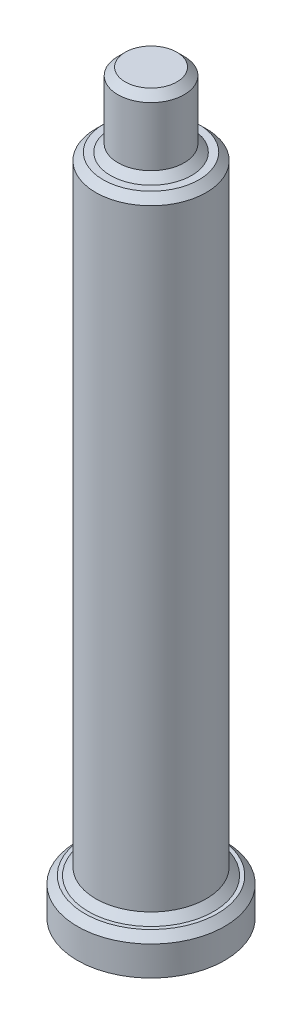
SolidWorks part; units mm, degrees
ref_plane "前视基准面" through (0, 0, 0) normal (0, 0, 1) x (1, 0, 0)
ref_plane "上视基准面" through (0, 0, 0) normal (0, 1, 0) x (1, 0, 0)
ref_plane "右视基准面" through (0, 0, 0) normal (1, 0, 0) x (0, 0, -1)
sketch "草图1" plane through (0, 0, 0) normal (0, 1, 0) x (1, 0, 0)
  circle A0 centre (0, 0) radius 1
  circle A1 centre (0, 0) radius 0.45
  circle A2 centre (0, 0) radius 0.75
  dimension "D1" = 2
  dimension "D2" = 1.5
  dimension "D3" = 0.9
extrude "凸台-拉伸1" add sketch "草图1" along normal blind 0.5 contours A0 A2 region at (-0.9717, 0, 0)
extrude "凸台-拉伸2" add sketch "草图1<4>" along normal blind 9 contours A2 A1 region at (-0.7288, 0, 0)
sketch "草图1<4>" plane through (0, 0, 0) normal (0, 1, 0) x (1, 0, 0) same geometry as "草图1"
extrude "凸台-拉伸3" add sketch "草图1<6>" along normal blind 10 contours A1 region at (0, 0, 0)
sketch "草图1<6>" plane through (0, 0, 0) normal (0, 1, 0) x (1, 0, 0) same geometry as "草图1"
chamfer "倒角3" distance 0.1 angle 45 1 edges at (0, 10, 0.45)
chamfer "倒角4" distance 0.1 angle 45 2 edges at (0, 0.5, 1) (0, 0.5, 0.75)
chamfer "倒角5" distance 0.1 angle 45 2 edges at (0, 9, 0.75) (0, 9, 0.45)
